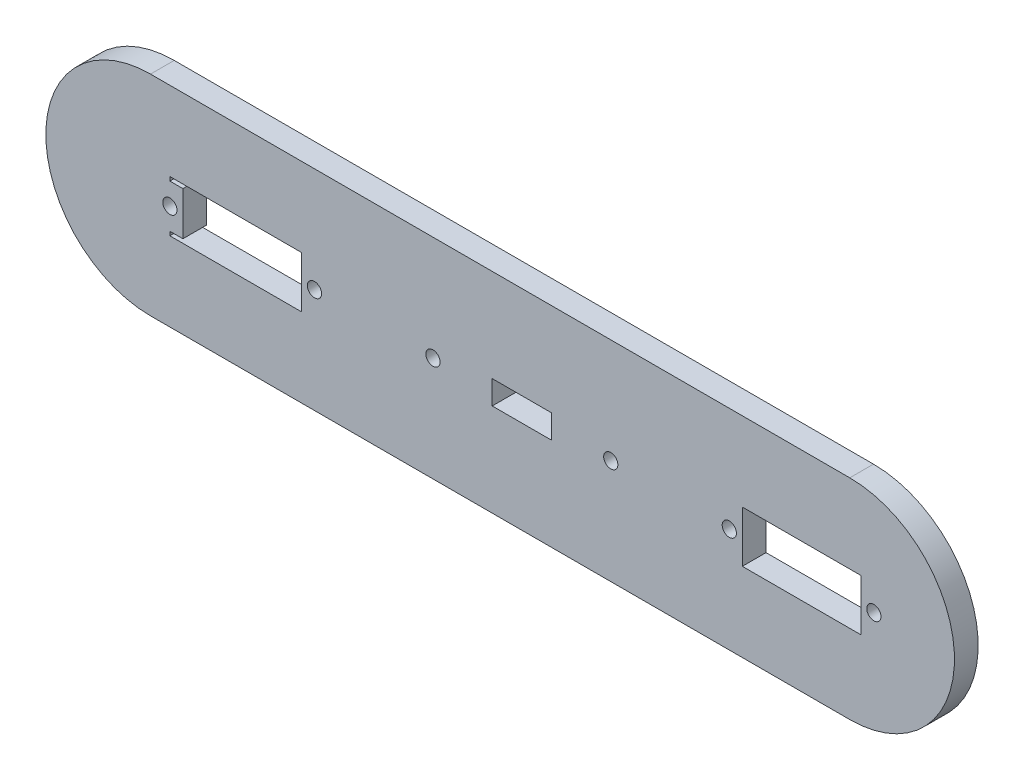
SolidWorks part; units mm, degrees
material "Balsa"
ref_plane "Plano frontal" through (0, 0, 0) normal (0, 0, 1) x (1, 0, 0)
ref_plane "Plano superior" through (0, 0, 0) normal (0, 1, 0) x (1, 0, 0)
ref_plane "Plano direito" through (0, 0, 0) normal (1, 0, 0) x (0, 0, -1)
sketch "Esboço1" plane through (0, 0, 0) normal (0, 0, 1) x (1, 0, 0)
  line L0 (-94, 26.5) -> (83, 26.5)
  line L1 (-94, -26.5) -> (83, -26.5)
  line L2 (-94, 0) -> (-20.7, 0) construction
  line L3 (-22.5, 0) -> (22.5, 0) construction
  line L4 (0, 11.6249) -> (0, -21.7831) construction
  line L5 (20.7, 0) -> (22.5, 0) construction
  line L6 (-89.1, 0) -> (-52.5, 0) construction
  line L7 (-7.5, -3) -> (7.5, -3)
  line L8 (-7.5, -3) -> (-7.5, 3)
  line L9 (-7.5, 3) -> (7.5, 3)
  line L10 (7.5, -3) -> (7.5, 3)
  line L11 (-7.5, -3) -> (7.5, 3) construction
  line L12 (-7.5, 3) -> (7.5, -3) construction
  line L13 (52.5, 0) -> (89.1, 0) construction
  line L14 (-85.8, -6.5) -> (-55.8, -6.5)
  line L15 (-85.8, -5.5) -> (-85.8, 5.5)
  line L16 (-85.8, 6.5) -> (-55.8, 6.5)
  line L17 (-55.8, -6.5) -> (-55.8, 6.5)
  line L18 (-85.8, -6.5) -> (-55.8, 6.5) construction
  line L19 (-85.8, 6.5) -> (-55.8, -6.5) construction
  line L20 (-85.8, 6.5) -> (-89.1, 6.5)
  line L21 (55.8, -6.5) -> (85.8, -6.5)
  line L22 (55.8, -6.5) -> (55.8, 6.5)
  line L23 (55.8, 6.5) -> (85.8, 6.5)
  line L24 (85.8, -6.5) -> (85.8, 6.5)
  line L25 (55.8, -6.5) -> (85.8, 6.5) construction
  line L26 (55.8, 6.5) -> (85.8, -6.5) construction
  line L27 (-89.1, 6.5) -> (-89.1, 5.5)
  line L28 (-89.1, 5.5) -> (-85.8, 5.5)
  line L29 (-89.1, -5.5) -> (-85.8, -5.5)
  line L30 (-89.1, -6.5) -> (-89.1, -5.5)
  line L31 (-85.8, -6.5) -> (-89.1, -6.5)
  arc A0 (83, -26.5) -> (83, 26.5) centre (83, 0) ccw
  arc A1 (-94, 26.5) -> (-94, -26.5) centre (-94, 0) ccw
  circle A4 centre (-22.5, 0) radius 1.8
  circle A5 centre (22.5, 0) radius 1.8
  circle A6 centre (-89.1, 0) radius 1.8
  circle A7 centre (-52.5, 0) radius 1.8
  circle A8 centre (52.5, 0) radius 1.8
  circle A9 centre (89.1, 0) radius 1.8
  point P8 (0, 0)
  point P19 (0, 0)
  point P29 (-70.8, 0)
  point P34 (70.8, 0)
  dimension "D1" = 3.6
  dimension "D5" = 15
  dimension "D6" = 26.5
  dimension "D7" = 3.6
  dimension "D2" = 45
  dimension "D3" = 83
  dimension "D4" = 94
  dimension "D8" = 36.6
  dimension "D9" = 30
  dimension "D10" = 6
  dimension "D11" = 13
  dimension "D12" = 30
  dimension "D13" = 1
extrude "Ressalto-extrusão1" add sketch "Esboço1" along normal blind 6
